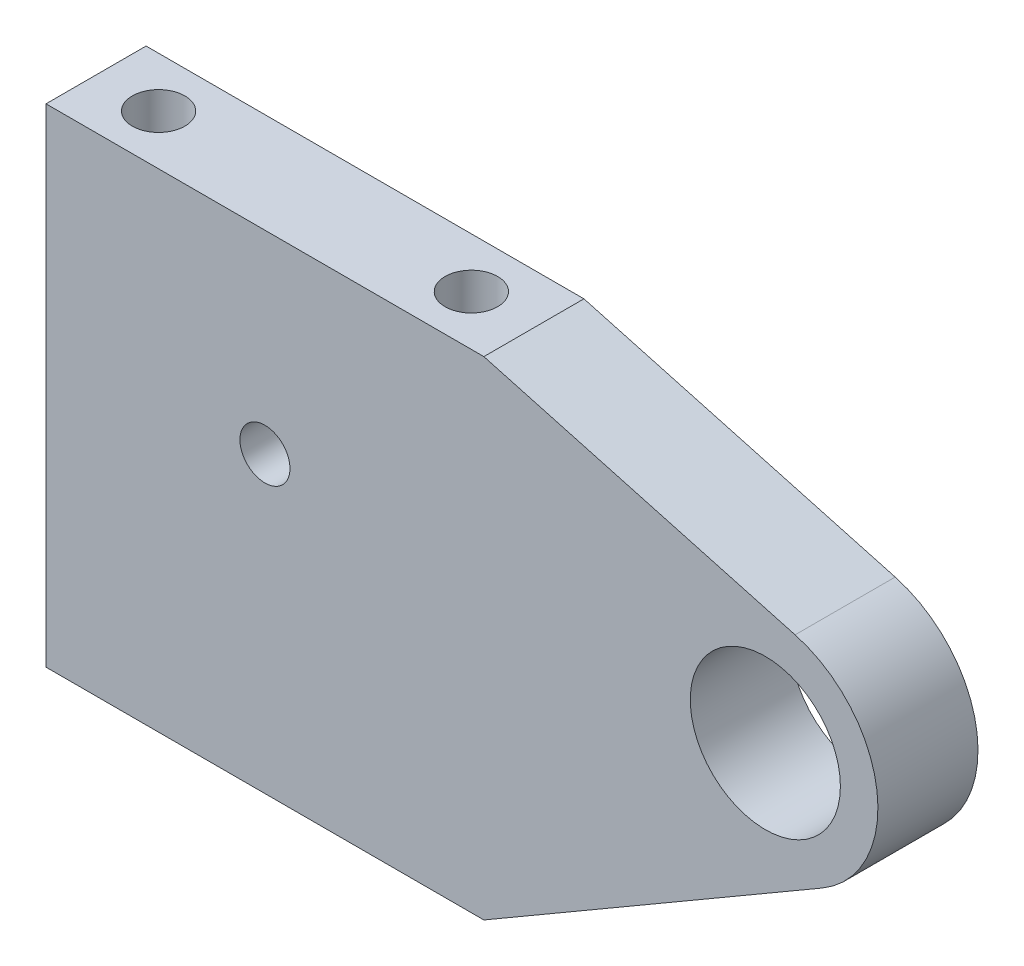
SolidWorks part; units mm, degrees
other "细节项目1"
material "6061-T6 (SS)"
ref_plane "前视基准面" through (0, 0, 0) normal (0, 0, 1) x (1, 0, 0)
ref_plane "上视基准面" through (0, 0, 0) normal (0, 1, 0) x (1, 0, 0)
ref_plane "右视基准面" through (0, 0, 0) normal (1, 0, 0) x (0, 0, -1)
sketch "草图1" plane through (0, 0, 0) normal (0, 0, 1) x (1, 0, 0)
  line L0 (17.5, 39) -> (17.5, 23.5) construction
  line L1 (0, 0) -> (35, 0)
  line L2 (0, 0) -> (0, 39)
  line L3 (0, 39) -> (35, 39)
  line L4 (35, 0) -> (35, 39)
  circle A0 centre (17.5, 23.5) radius 2
  dimension "D3" = 4
  dimension "D1" = 39
  dimension "D2" = 35
  dimension "D4" = 15.5
extrude "凸台-拉伸1" add sketch "草图1" along normal blind 8
cosmetic thread "装饰螺纹线5" parameters "D2"=5
sketch "草图2" plane through (0, 39, 0) normal (0, 1, 0) x (1, 0, 0)
  line L0 (0, -4) -> (5, -4) construction
  line L1 (0, -8) -> (0, 0) construction
  line L2 (5, -4) -> (30, -4) construction
  line L3 (30, -4) -> (35, -4) construction
  line L4 (35, -8) -> (35, 0) construction
  circle A0 centre (5, -4) radius 2.1
  circle A1 centre (30, -4) radius 2.1
  dimension "D2" = 4.2
  dimension "D1" = 25
extrude "切除-拉伸1" cut sketch "草图2" against normal through all
sketch "草图5" plane through (0, 0, 8) normal (0, 0, 1) x (1, 0, 0)
  line L0 (35, 39) -> (59.8794, 32.1798)
  line L1 (62.0253, 15.7204) -> (35, 0)
  line L2 (35, 0) -> (35, 39)
  line L3 (17.5, 23.5) -> (57.5, 23.5) construction
  circle A0 centre (57.5, 23.5) radius 6
  arc A1 (59.8794, 32.1798) -> (62.0253, 15.7204) centre (57.5, 23.5) cw
  dimension "D1" = 12
  dimension "D2" = 9
  dimension "D3" = 40
extrude "凸台-拉伸3" add sketch "草图5" against normal up to surface (8 mm away) up to face at (17.5, 19.5, 0)
